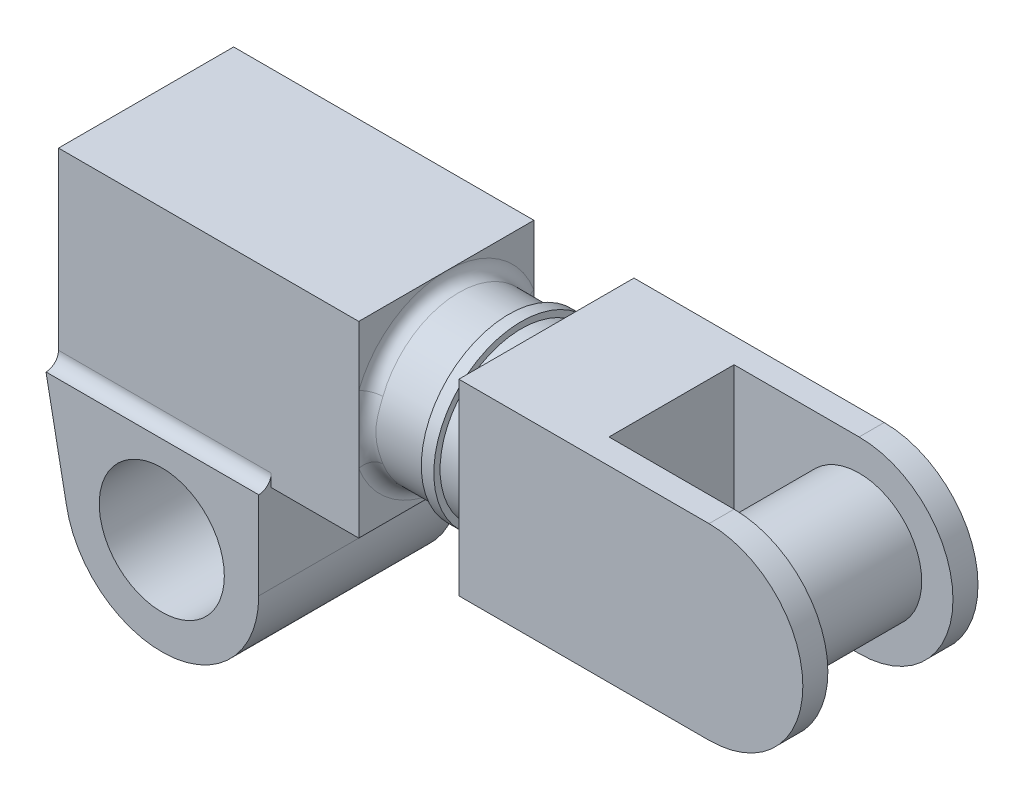
SolidWorks part; units mm, degrees
ref_plane "Front Plane" through (0, 0, 0) normal (0, 0, 1) x (1, 0, 0)
ref_plane "Top Plane" through (0, 0, 0) normal (0, 1, 0) x (1, 0, 0)
ref_plane "Right Plane" through (0, 0, 0) normal (1, 0, 0) x (0, 0, -1)
sketch "Sketch1" plane through (0, 0, 0) normal (1, 0, 0) x (0, 0, -1)
  line L1 (70, 75) -> (-70, 75)
  line L2 (70, 75) -> (70, -75)
  line L3 (70, -75) -> (-70, -75)
  line L4 (-70, 75) -> (-70, -75)
  line L5 (70, 75) -> (-70, -75) construction
  line L6 (70, -75) -> (-70, 75) construction
  point P0 (0, 0)
  dimension "D1" = 150
  dimension "D2" = 140
extrude "Boss-Extrude1" add sketch "Sketch1" along normal blind 240
sketch "Sketch2" plane through (240, 0, 0) normal (1, 0, 0) x (0, 0, -1)
  circle A0 centre (0, 0) radius 65
  dimension "D1" = 130
extrude "Boss-Extrude2" add sketch "Sketch2" along normal blind 50
sketch "Sketch3" plane through (290, 0, 0) normal (1, 0, 0) x (0, 0, -1)
  circle A0 centre (0, 0) radius 70
  dimension "D1" = 140
extrude "Boss-Extrude3" add sketch "Sketch3" along normal blind 10
sketch "Sketch4" plane through (0, 0, 0) normal (0, 0, 1) x (1, 0, 0)
  line L0 (0, -75) -> (16.2188, -158.4383)
  line L1 (0, 75) -> (0, -75) construction
  line L2 (170.0448, -145) -> (170.0448, -75)
  line L3 (240, -75) -> (0, -75) construction
  line L4 (0, -75) -> (170.0448, -75)
  circle A0 centre (92.5448, -145) radius 50
  arc A1 (16.2188, -158.4383) -> (170.0448, -145) centre (92.5448, -145) ccw
  dimension "D1" = 155
  dimension "D2" = 100
  dimension "D3" = 191
  dimension "D4" = 85
  dimension "D5" = 70
extrude "Boss-Extrude4" add sketch "Sketch4" along normal mid plane 160
fillet "Fillet1" radius 10 3 edges at (85.0224, -75, -70) (240, 0, -65) (85.0224, -75, 70)
sketch "Sketch5" plane through (300, 0, 0) normal (1, 0, 0) x (0, 0, -1)
  circle A0 centre (0, 0) radius 65
  dimension "D1" = 130
extrude "Boss-Extrude5" add sketch "Sketch5" along normal blind 20
sketch "Sketch6" plane through (0, 0, 0) normal (0, 0, 1) x (1, 0, 0)
  line L0 (520, 75) -> (320, 75)
  line L1 (320, 75) -> (320, -75)
  line L2 (320, -75) -> (520, -75)
  line L3 (320, -65) -> (320, 65) construction
  arc A0 (520, -75) -> (520, 75) centre (520, 0) ccw
  dimension "D1" = 150
  dimension "D2" = 200
extrude "Boss-Extrude6" add sketch "Sketch6" along normal mid plane 140
sketch "Sketch7" plane through (0, 0, 0) normal (0, 0, 1) x (1, 0, 0)
  line L0 (520, 75) -> (420, 75)
  line L1 (520, 75) -> (320, 75) construction
  line L2 (420, 75) -> (420, -75)
  line L3 (320, -75) -> (520, -75) construction
  line L4 (420, -75) -> (520, -75)
  arc A0 (520, -75) -> (520, 75) centre (520, 0) ccw construction
  arc A1 (520, -75) -> (520, 75) centre (520, 0) ccw
extrude "Cut-Extrude1" cut sketch "Sketch7" against normal mid plane 100
sketch "Sketch8" plane through (0, 0, -50) normal (0, 0, 1) x (1, 0, 0)
  circle A0 centre (520, 0) radius 50
  dimension "D1" = 100
extrude "Boss-Extrude7" add sketch "Sketch8" along normal blind 100
